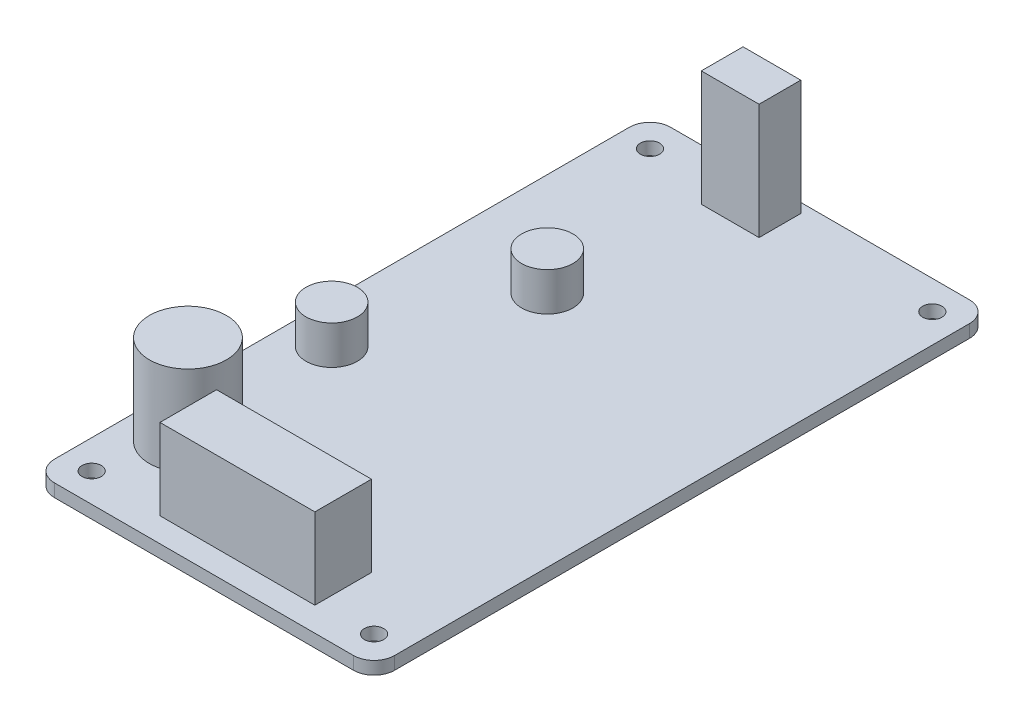
SolidWorks part; units mm, degrees
ref_plane "Front Plane" through (0, 0, 0) normal (0, 0, 1) x (1, 0, 0)
ref_plane "Top Plane" through (0, 0, 0) normal (0, 1, 0) x (1, 0, 0)
ref_plane "Right Plane" through (0, 0, 0) normal (1, 0, 0) x (0, 0, -1)
sketch "Sketch1" plane through (0, 0, 0) normal (0, 1, 0) x (1, 0, 0)
  line L0 (-21.0344, 0) -> (21.0344, 0) construction
  line L1 (18.4944, -38.1) -> (-18.4944, -38.1)
  line L2 (21.0344, -35.56) -> (21.0344, 35.56)
  line L3 (18.4944, 38.1) -> (-18.4944, 38.1)
  line L4 (-21.0344, -35.56) -> (-21.0344, 35.56)
  line L5 (21.0344, -38.1) -> (-21.0344, 38.1) construction
  line L6 (21.0344, 38.1) -> (-21.0344, -38.1) construction
  line L8 (0, 38.1) -> (0, -38.1) construction
  line L9 (-8.3344, 36.9094) -> (-1.1906, 36.9094)
  line L10 (-8.3344, 36.9094) -> (-8.3344, 31.75)
  line L11 (-8.3344, 31.75) -> (-1.1906, 31.75)
  line L12 (-1.1906, 36.9094) -> (-1.1906, 31.75)
  line L13 (-8.3344, 36.9094) -> (-1.1906, 31.75) construction
  line L14 (-8.3344, 31.75) -> (-1.1906, 36.9094) construction
  line L15 (-8.4455, -28.1) -> (10.7156, -28.1)
  line L16 (-8.4455, -28.1) -> (-8.4455, -35.1)
  line L17 (-8.4455, -35.1) -> (10.7156, -35.1)
  line L18 (10.7156, -28.1) -> (10.7156, -35.1)
  line L19 (-8.4455, -28.1) -> (10.7156, -35.1) construction
  line L20 (-8.4455, -35.1) -> (10.7156, -28.1) construction
  arc A0 (-18.4944, -38.1) -> (-21.0344, -35.56) centre (-18.4944, -35.56) cw
  arc A1 (18.4944, -38.1) -> (21.0344, -35.56) centre (18.4944, -35.56) ccw
  arc A2 (21.0344, 35.56) -> (18.4944, 38.1) centre (18.4944, 35.56) ccw
  arc A3 (-18.4944, 38.1) -> (-21.0344, 35.56) centre (-18.4944, 35.56) ccw
  circle A4 centre (-17.4625, 34.5281) radius 1.1906
  circle A5 centre (17.4625, 34.5281) radius 1.1906
  circle A6 centre (17.4625, -34.5281) radius 1.1906
  circle A7 centre (-17.4625, -34.5281) radius 1.1906
  point P0 (0, 0)
  point P30 (-4.7625, 34.3297)
  point P35 (1.1351, -31.6)
  dimension "D3" = 2.54
  dimension "D4" = 3.5719
  dimension "D5" = 2.3813
  dimension "D6" = 3.5719
  dimension "D13" = 9.017
  dimension "D1" = 76.2
  dimension "D2" = 42.0688
  dimension "D7" = 19.8438
  dimension "D8" = 29.3687
  dimension "D9" = 6.35
  dimension "D10" = 1.1906
  dimension "D12" = 31.75
  dimension "D14" = 10
  dimension "D15" = 7
extrude "Boss-Extrude1" add sketch "Sketch1" along normal blind 14.2875 contours L10 L11 L12 L9
extrude "Boss-Extrude2" add sketch "Sketch1<3>" along normal blind 10 separate body contours L15 L18 L17 L16
sketch "Sketch1<3>" plane through (0, 0, 0) normal (0, 1, 0) x (1, 0, 0) same geometry as "Sketch1"
extrude "Boss-Extrude3" add sketch "Sketch1<4>" against normal blind 1.5875 contours L4 A3 L3 A2 L2 A1 L1 A0
sketch "Sketch1<4>" plane through (0, 0, 0) normal (0, 1, 0) x (1, 0, 0) same geometry as "Sketch1"
extrude "Cut-Extrude1" cut sketch "Sketch1<5>" against normal blind 1.5875 contours A4 | A7 | A6 | A5 region at (-17.4625, 0, -34.5281) region at (17.4625, 0, 34.5281) region at (-17.4625, 0, 34.5281)
sketch "Sketch1<5>" plane through (0, 0, 0) normal (0, 1, 0) x (1, 0, 0) same geometry as "Sketch1"
sketch "Sketch2" plane through (0, 0, 0) normal (0, 1, 0) x (1, 0, 0)
  line L0 (18.4944, -38.1) -> (-18.4944, -38.1) construction
  line L1 (-21.0344, -35.56) -> (-21.0344, 35.56) construction
  circle A0 centre (-14.6844, -25.4) radius 4.7625
  circle A1 centre (-15.9544, -6.35) radius 3.175
  circle A2 centre (-8.3344, 12.7) radius 3.175
  dimension "D1" = 9.525
  dimension "D2" = 6.35
  dimension "D3" = 12.7
  dimension "D4" = 6.35
  dimension "D5" = 31.75
  dimension "D6" = 50.8
  dimension "D7" = 12.7
  dimension "D8" = 5.08
extrude "Boss-Extrude4" add sketch "Sketch2" along normal blind 11.1125 contours A0 region at (-14.6844, 0, 25.4)
extrude "Boss-Extrude5" add sketch "Sketch2<3>" along normal blind 4.7625 contours A1 | A2 region at (-15.9544, 0, 6.35) region at (-8.3344, 0, -12.7)
sketch "Sketch2<3>" plane through (0, 0, 0) normal (0, 1, 0) x (1, 0, 0) same geometry as "Sketch2"
